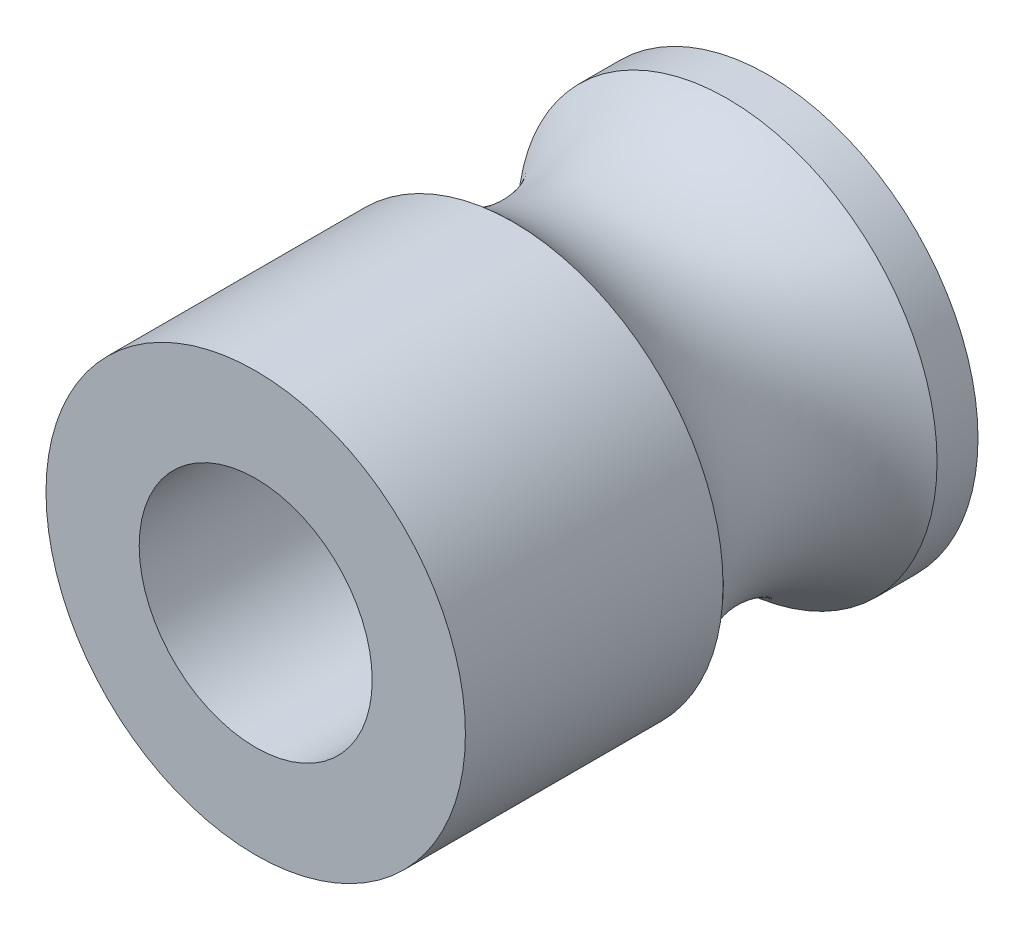
SolidWorks part; units mm, degrees
ref_plane "Front Plane" through (0, 0, 0) normal (0, 0, 1) x (1, 0, 0)
ref_plane "Top Plane" through (0, 0, 0) normal (0, 1, 0) x (1, 0, 0)
ref_plane "Right Plane" through (0, 0, 0) normal (1, 0, 0) x (0, 0, -1)
sketch "Sketch1" plane through (0, 0, 0) normal (0, 1, 0) x (1, 0, 0)
  line L0 (4.5, 0) -> (0, 0)
  line L1 (0, 0) -> (0, -11)
  line L2 (0, -11) -> (4.5, -11)
  line L3 (4.5, -11) -> (4.5, -5.4712)
  line L4 (4.5, -0.8788) -> (4.5, 0)
  line L5 (0, 0) -> (0, -11) construction
  arc A0 (4.5, -5.4712) -> (4.5, -0.8788) centre (6.8, -3.175) cw
  point P7 (0, 0)
  dimension "D4" = 3.55
  dimension "D5" = 3.25
  dimension "D1" = 4.5
  dimension "D2" = 11
  dimension "D3" = 3.175
revolve "Revolve1" add sketch "Sketch1" angle 360 about L5 reverse direction yes
hole_wizard "Ø5.0 (5) Diameter Hole1" positions "Sketch3" profile "Sketch2" hole size "Ø5.0" standard "ANSI Metric"
sketch "Sketch3" plane through (0, 0, 11) normal (0, 0, 1) x (1, 0, 0)
  point P0 (0, 0)
sketch "Sketch2" plane through (0, 0, 11) normal (1, 0, 0) x (0, -1, 0)
  line L0 (0, 0) -> (0, 11)
  line L1 (0, 11) -> (2.5, 11)
  line L2 (2.5, 11) -> (2.5, 0)
  line L5 (2.5, 0) -> (0, 0)
  line L11 (0, -6.35) -> (0, 107.95) construction
  dimension "Thru Hole Dia." = 5
  dimension "Thru Hole Depth" = 11
